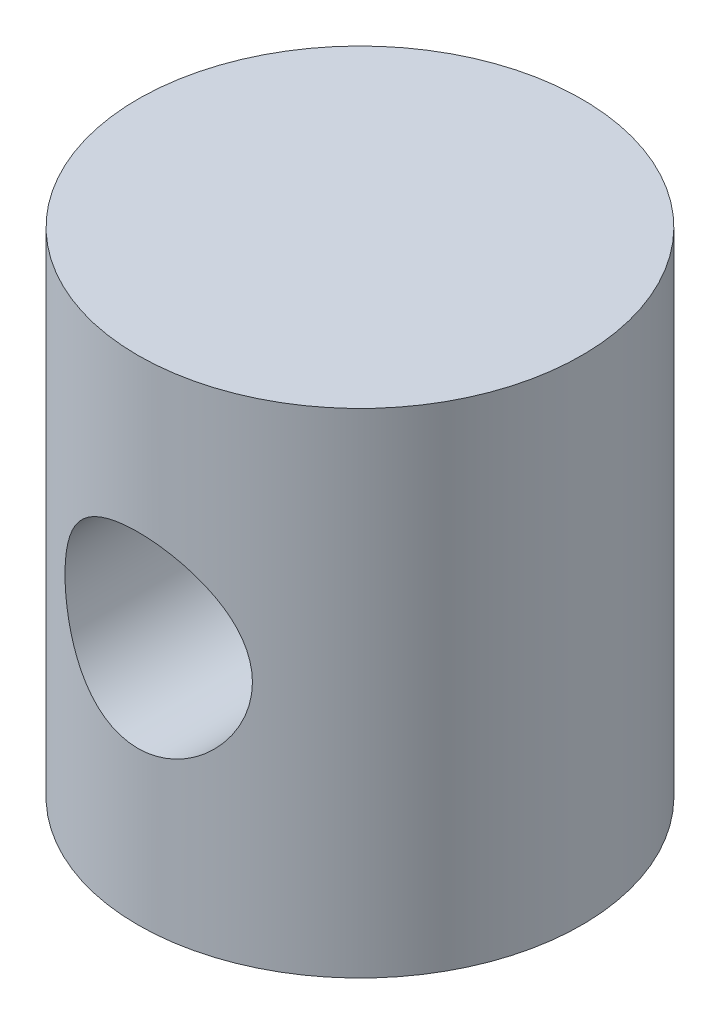
SolidWorks part; units mm, degrees
ref_plane "Front Plane" through (0, 0, 0) normal (0, 0, 1) x (1, 0, 0)
ref_plane "Top Plane" through (0, 0, 0) normal (0, 1, 0) x (1, 0, 0)
ref_plane "Right Plane" through (0, 0, 0) normal (1, 0, 0) x (0, 0, -1)
sketch "Sketch3" plane through (0, 0, 0) normal (0, 1, 0) x (1, 0, 0)
  circle A0 centre (0, 0) radius 4.5
  dimension "D1" = 9
extrude "Boss-Extrude1" add sketch "Sketch3" along normal blind 10
sketch "Sketch4" plane through (0, 0, 0) normal (0, 0, 1) x (1, 0, 0)
  line L0 (-4.5, 5) -> (-1.6, 5)
  line L1 (-4.5, 10) -> (-4.5, 0) construction
  line L2 (4.5, 0) -> (4.5, 10) construction
  line L3 (1.6, 5) -> (4.5, 5)
  circle A0 centre (0, 5) radius 1.6
  dimension "D1" = 3.2
sketch "Sketch5" plane through (0, 0, 0) normal (0, 0, 1) x (1, 0, 0)
  circle A1 centre (0, 5) radius 1.9
  dimension "D1" = 3.8
extrude "Cut-Extrude1" cut sketch "Sketch5" against normal through all both and the other way through all
